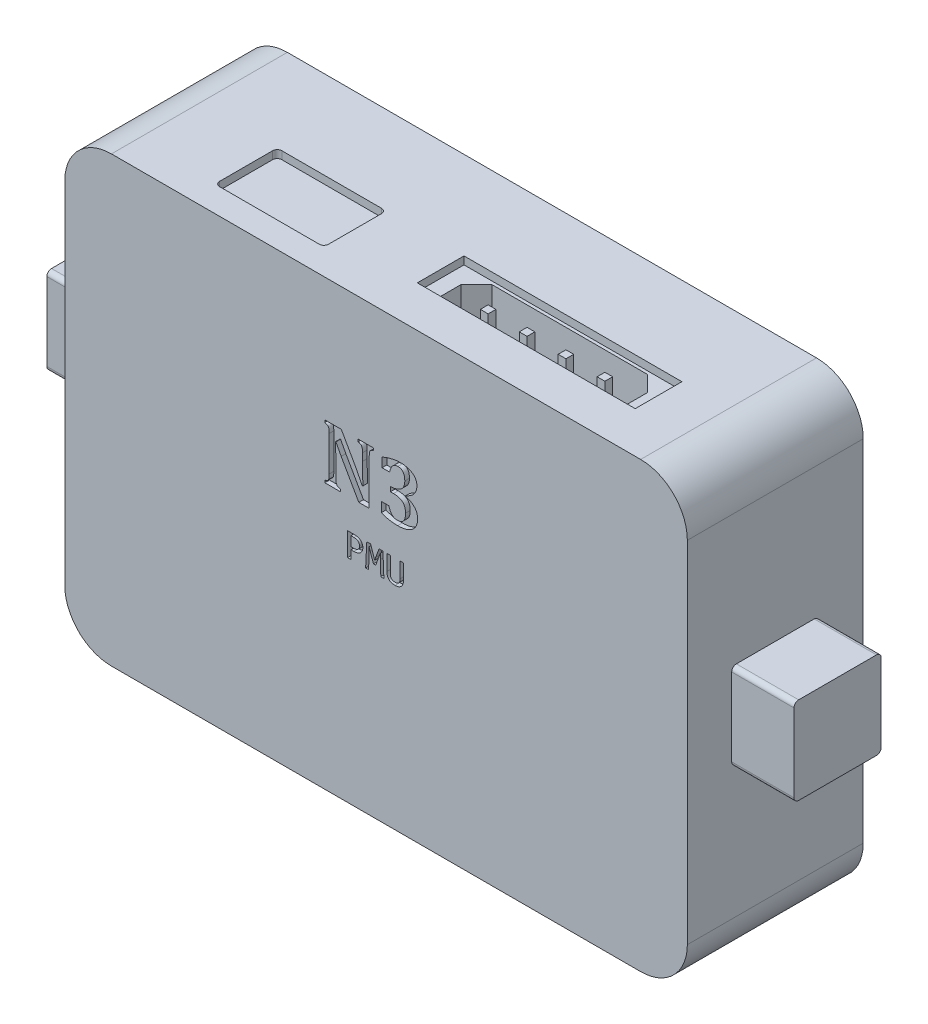
SolidWorks part; units mm, degrees
ref_plane "前视基准面" through (0, 0, 0) normal (0, 0, 1) x (1, 0, 0)
ref_plane "上视基准面" through (0, 0, 0) normal (0, 1, 0) x (1, 0, 0)
ref_plane "右视基准面" through (0, 0, 0) normal (1, 0, 0) x (0, 0, -1)
sketch "Main" plane through (0, 0, 0) normal (0, 0, 1) x (1, 0, 0)
  line L0 (-20, 11.25) -> (-20, -11.25)
  line L1 (0, 0) -> (30.1154, 0) construction
  line L2 (0, -7.3749) -> (0, 9.6594) construction
  line L3 (-17, 14.25) -> (17, 14.25)
  line L4 (20, 11.25) -> (20, -11.25)
  line L5 (-17, -14.25) -> (17, -14.25)
  arc A0 (-20, 11.25) -> (-17, 14.25) centre (-17, 11.25) cw
  arc A1 (20, 11.25) -> (17, 14.25) centre (17, 11.25) ccw
  arc A2 (20, -11.25) -> (17, -14.25) centre (17, -11.25) cw
  arc A3 (-20, -11.25) -> (-17, -14.25) centre (-17, -11.25) ccw
  point P6 (-20, 0)
  point P12 (0, 14.25)
  dimension "D2" = 3
  dimension "D1" = 20
  dimension "D4" = 14.25
extrude "凸台-拉伸1" add sketch "Main" along normal mid plane 11.3
sketch "草图3" plane through (0, 0, 5.65) normal (0, 0, 1) x (1, 0, 0)
  line L0 (0, 0) -> (18.2534, 0) construction
  line L1 (0, 0) -> (0, 13.6083) construction
  text T0 "N3" font "Cambria" height 3.5
  text T1 "PMU" font "Consolas" height 1.5
  dimension "D1" = 3.55
  dimension "D2" = 2
extrude "切除-拉伸3" cut sketch "草图3" against normal blind 0.3
sketch "Up_iBat" plane through (0, 14.25, 0) normal (0, 1, 0) x (1, 0, 0)
  line L0 (-21.0547, 0) -> (21.0547, 0) construction
  line B0 (-11.7, 0) -> (-5.3, 0)
  line B1 (-12, -0.3) -> (-12, -3.7)
  line B2 (-11.7, -4) -> (-5.3, -4)
  line B3 (-5, -0.3) -> (-5, -3.7)
  arc B4 (-12, -0.3) -> (-11.7, 0) centre (-11.7, -0.3) cw
  arc B5 (-12, -3.7) -> (-11.7, -4) centre (-11.7, -3.7) ccw
  arc B6 (-5, -3.7) -> (-5.3, -4) centre (-5.3, -3.7) cw
  arc B7 (-5, -0.3) -> (-5.3, 0) centre (-5.3, -0.3) ccw
sketch_block_instance "Pin_3-1"
sketch_block "Pin_3" parameters "D1"=0.3, "D2"=7, "D3"=4
sketch "草图6" plane through (20, 0, 0) normal (1, 0, 0) x (0, 0, -1)
  line L0 (-2.5, 2.8) -> (2.5, 2.8)
  line L1 (-2.8, 2.5) -> (-2.8, -2.5)
  line L2 (-2.5, -2.8) -> (2.5, -2.8)
  line L3 (2.8, 2.5) -> (2.8, -2.5)
  arc A0 (-2.8, 2.5) -> (-2.5, 2.8) centre (-2.5, 2.5) cw
  arc A1 (-2.8, -2.5) -> (-2.5, -2.8) centre (-2.5, -2.5) ccw
  arc A2 (2.8, -2.5) -> (2.5, -2.8) centre (2.5, -2.5) cw
  arc A3 (2.8, 2.5) -> (2.5, 2.8) centre (2.5, 2.5) ccw
  dimension "D1" = 0.3
  dimension "D2" = 5.6
  dimension "D3" = 5.6
  dimension "D4" = 2.8
  dimension "D5" = 2.8
extrude "凸台-拉伸3" add sketch "草图6" along normal blind 4 contours L0 A3 L3 A2 L2 A1 L1 A0
sketch "草图7" plane through (-20, 0, 0) normal (-1, 0, 0) x (0, 0, 1)
  line L0 (-2.5, 2.8) -> (2.5, 2.8)
  line L1 (-2.8, 2.5) -> (-2.8, -2.5)
  line L2 (-2.5, -2.8) -> (2.5, -2.8)
  line L3 (2.8, 2.5) -> (2.8, -2.5)
  arc A0 (-2.8, 2.5) -> (-2.5, 2.8) centre (-2.5, 2.5) cw
  arc A1 (-2.8, -2.5) -> (-2.5, -2.8) centre (-2.5, -2.5) ccw
  arc A2 (2.8, -2.5) -> (2.5, -2.8) centre (2.5, -2.5) cw
  arc A3 (2.8, 2.5) -> (2.5, 2.8) centre (2.5, 2.5) ccw
  dimension "D1" = 0.3
  dimension "D2" = 5.6
  dimension "D3" = 5.6
  dimension "D4" = 2.8
  dimension "D5" = 2.8
extrude "凸台-拉伸4" add sketch "草图7" along normal blind 4 contours L0 A3 L3 A2 L2 A1 L1 A0
sketch "UP_CAN" plane through (0, 14.25, 0) normal (0, 1, 0) x (-1, 0, 0)
  line L0 (-23.1031, 1.2) -> (5.9887, 1.2) construction
  line L1 (-7, 7.1525) -> (-7, -6.7525) construction
  line L2 (-1, 2.7) -> (-13, 2.7)
  line L3 (-2, 0.2) -> (-12, 0.2)
  line L4 (-1, 2.7) -> (-1, 1.2)
  line L5 (-13, 2.7) -> (-13, 1.2)
  line L6 (-2, 0.2) -> (-1, 1.2)
  line L7 (-12, 0.2) -> (-13, 1.2)
  line L8 (21.0547, 0) -> (-21.0547, 0) construction
  line L9 (0, 0) -> (0, 3)
  line L10 (0, 3) -> (-14, 3)
  line L11 (-14, 3) -> (-14, 0)
  line L12 (-14, 0) -> (0, 0)
  line L13 (-8, 1.45) -> (-8, 1.95)
  line L14 (-10.5, 1.45) -> (-11, 1.45)
  line L15 (-10.5, 1.45) -> (-10.5, 1.95)
  line L16 (-10.5, 1.95) -> (-11, 1.95)
  line L17 (-11, 1.45) -> (-11, 1.95)
  line L18 (-8, 1.45) -> (-8.5, 1.45)
  line L19 (-8.5, 1.45) -> (-8.5, 1.95)
  line L20 (-8, 1.95) -> (-8.5, 1.95)
  line L21 (-5.5, 1.45) -> (-5.5, 1.95)
  line L22 (-5.5, 1.45) -> (-6, 1.45)
  line L23 (-6, 1.45) -> (-6, 1.95)
  line L24 (-5.5, 1.95) -> (-6, 1.95)
  line L25 (-3, 1.45) -> (-3, 1.95)
  line L26 (-3, 1.45) -> (-3.5, 1.45)
  line L27 (-3.5, 1.45) -> (-3.5, 1.95)
  line L28 (-3, 1.95) -> (-3.5, 1.95)
  line L29 (-10.5, 1.45) -> (-8, 1.45) construction
  point P7 (-7, 2.7)
  point P10 (-7, 0.2)
  dimension "D1" = 12
  dimension "D2" = 10
  dimension "D3" = 2.5
  dimension "D4" = 1.5
  dimension "D5" = 7
  dimension "D6" = 14
  dimension "D7" = 3
  dimension "D8" = 7
  dimension "D9" = 0.2
  dimension "D10" = 0.5
  dimension "D11" = 0.5
  dimension "D12" = 2.5
  dimension "D13" = 0.75
  dimension "D15" = 2.5
  dimension "D14" = 4
extrude "切除-拉伸5" cut sketch "UP_CAN" against normal blind 4 contours L7 L3 L6 L4 L2 L5 region at (7, 14.25, 1.4738)
extrude "切除-拉伸6" cut sketch "UP_CAN<3>" against normal blind 0.5 contours L12 L9 L10 L11
sketch "UP_CAN<3>" plane through (0, 14.25, 0) normal (0, 1, 0) x (-1, 0, 0) same geometry as "UP_CAN"
extrude "切除-拉伸7" cut sketch "Up_iBat" against normal blind 0.5
